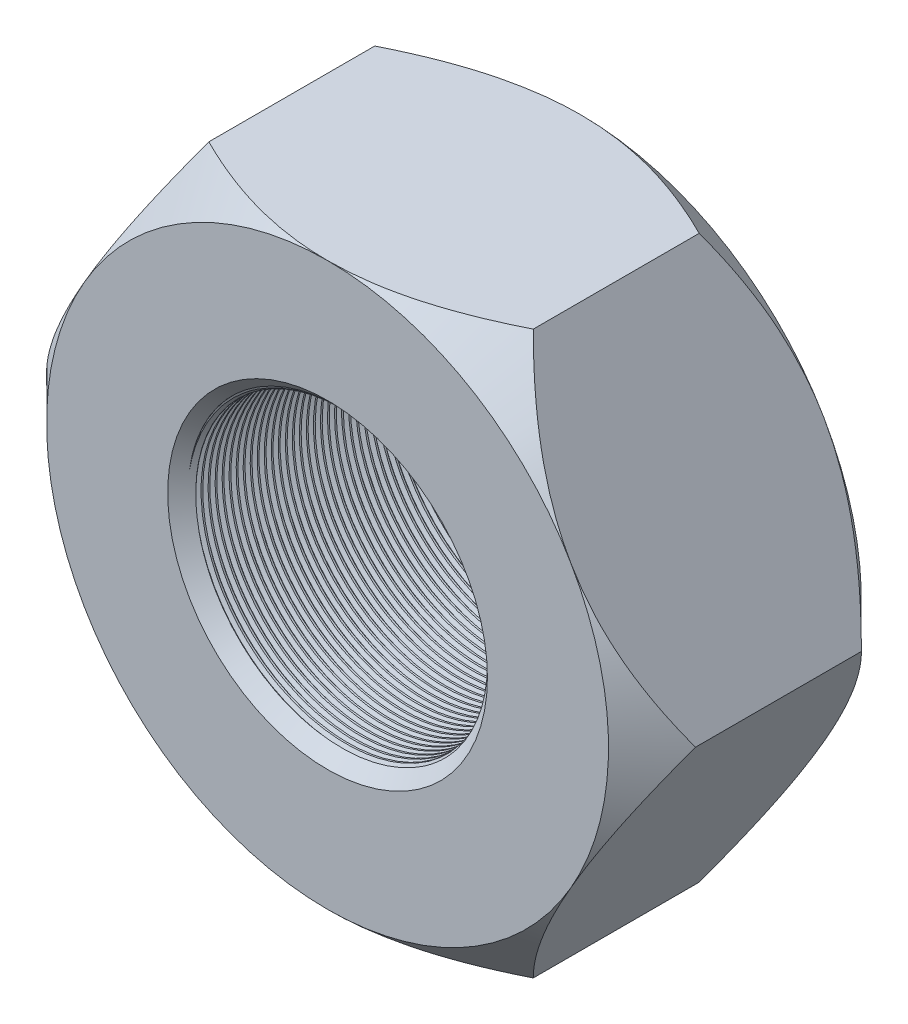
SolidWorks part; units mm, degrees
ref_plane "Front Plane" through (0, 0, 0) normal (0, 0, 1) x (1, 0, 0)
ref_plane "Top Plane" through (0, 0, 0) normal (0, 1, 0) x (1, 0, 0)
ref_plane "Right Plane" through (0, 0, 0) normal (1, 0, 0) x (0, 0, -1)
sketch "Sketch1" plane through (0, 0, 0) normal (0, 0, 1) x (1, 0, 0)
  line L1 (-5.7735, -10) -> (5.7735, -10)
  line L2 (5.7735, -10) -> (11.547, 0)
  line L3 (11.547, 0) -> (5.7735, 10)
  line L4 (5.7735, 10) -> (-5.7735, 10)
  line L5 (-5.7735, 10) -> (-11.547, 0)
  line L6 (-11.547, 0) -> (-5.7735, -10)
  circle A0 centre (0, 0) radius 10 construction
  dimension "D1" = 20
extrude "Boss-Extrude1" add sketch "Sketch1" along normal mid plane 9
sketch "Sketch2" plane through (0, 0, -4.5) normal (0, 0, -1) x (-1, 0, 0)
  line L0 (11.547, 0) -> (5.7735, -10) construction
  circle A0 centre (0, 0) radius 10
extrude "Cut-Extrude1" cut sketch "Sketch2" against normal through all draft 45 flip side to cut
mirror "Mirror1" about plane through (0, 0, 0) normal (0, 0, 1) of "Cut-Extrude1"
sketch "Sketch3" plane through (0, 0, -4.5) normal (0, 0, -1) x (-1, 0, 0)
  circle A0 centre (0, 0) radius 5.19
  dimension "D1" = 10.38
extrude "Cut-Extrude2" cut sketch "Sketch3" against normal through all
chamfer "Chamfer1" distance 0.5 angle 45 2 edges at (-5.19, 0, 4.5) (-5.19, 0, -4.5)
thread "Thread1" pitch 0.25 profile "Thread Profile3" start angle 0, offset 2, length 0, pitch 0.25, diameter 10.38
ref_plane "Plane3" through (-5.19, 0, 6) normal (0, -1, 0) x (-1, 0, 0)
sketch "Thread Profile3" plane through (-5.19, 0, 6) normal (0, -1, 0) x (-1, 0, 0)
  line L0 (0, 0) -> (0, 0.25) construction
  line L1 (0, 0) -> (0.1353, 0.0781)
  line L2 (0.1353, 0.0781) -> (0.1353, 0.1094)
  line L3 (0.1353, 0.1094) -> (0, 0.1875)
  line L4 (0.1353, 0.0937) -> (0, 0.0937) construction
  line L11 (0, 0) -> (0, 0.1875)
  point P2 (0, 0)
  dimension "Pitch" = 0.25
  dimension "Profile_Angle" = 60
  dimension "Profile_Land" = 0.0312
  dimension "Profile_Height" = 0.1353
